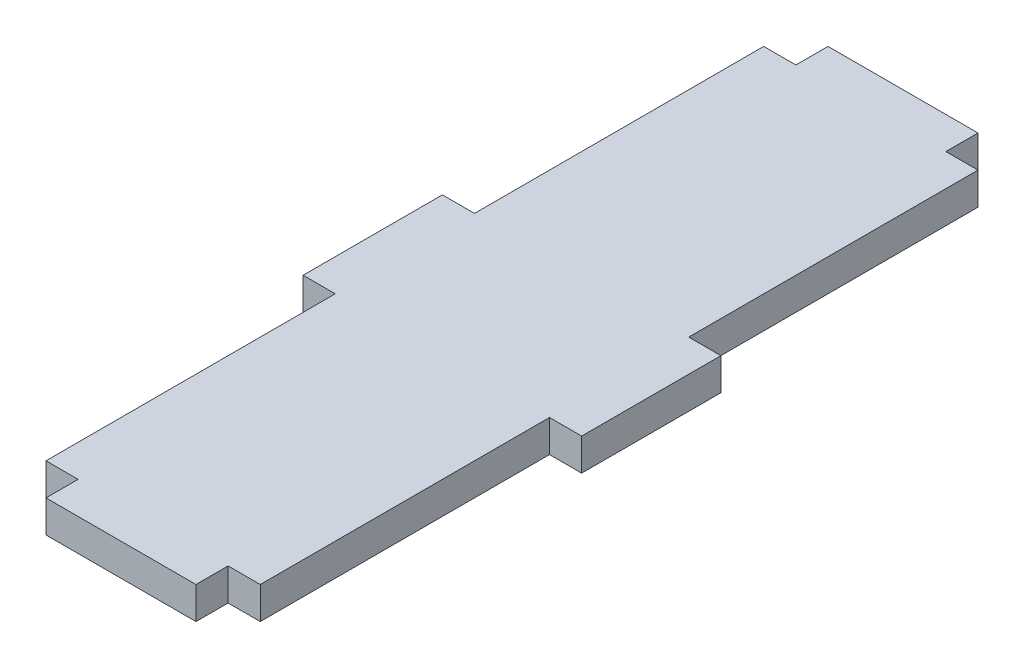
SolidWorks part; units mm, degrees
ref_plane "Alzado" through (0, 0, 0) normal (0, 0, 1) x (1, 0, 0)
ref_plane "Planta" through (0, 0, 0) normal (0, 1, 0) x (1, 0, 0)
ref_plane "Vista lateral" through (0, 0, 0) normal (1, 0, 0) x (0, 0, -1)
sketch "Croquis2" plane through (0, 0, 0) normal (0, 1, 0) x (1, 0, 0)
  line L1 (-4.5, 22) -> (-4.5, 9)
  line L2 (15.5, -21) -> (15.5, -18)
  line L3 (15.5, 49) -> (15.5, 52)
  line L4 (15.5, 52) -> (1.5, 52)
  line L5 (18.5, -18) -> (15.5, -18)
  line L6 (1.5, 52) -> (1.5, 49)
  line L7 (15.5, 52) -> (15.5, 49)
  line L8 (-1.5, 49) -> (1.5, 49)
  line L9 (18.5, 49) -> (18.5, 22)
  line L10 (-1.5, 9) -> (-4.5, 9)
  line L11 (-1.5, -18) -> (-1.5, 9)
  line L12 (15.5, -18) -> (15.5, -21)
  line L13 (1.5, 49) -> (1.5, 52)
  line L14 (-1.5, 49) -> (-1.5, 22)
  line L15 (-1.5, 22) -> (-4.5, 22)
  line L16 (15.5, 49) -> (18.5, 49)
  line L17 (1.5, -18) -> (1.5, -21)
  line L18 (18.5, -18) -> (18.5, 9)
  line L19 (18.5, 9) -> (21.5, 9)
  line L20 (-1.5, -18) -> (1.5, -18)
  line L21 (21.5, 22) -> (21.5, 9)
  line L22 (1.5, -21) -> (1.5, -18)
  line L23 (15.5, -21) -> (1.5, -21)
  line L24 (18.5, 22) -> (21.5, 22)
  dimension "D1" = 13
  dimension "D2" = 27
  dimension "D3" = 14
  dimension "D4" = 3
  dimension "D5" = 27
  dimension "D6" = 13
  dimension "D7" = 27
  dimension "D9" = 27
  dimension "D10" = 3
  dimension "D11" = 3
  dimension "D13" = 3
extrude "Saliente-Extruir1" add sketch "Croquis2" along normal blind 3 contours L23 L9 L8 L10 L11 L20 L17 region at (8.5, 0, -15.5)
